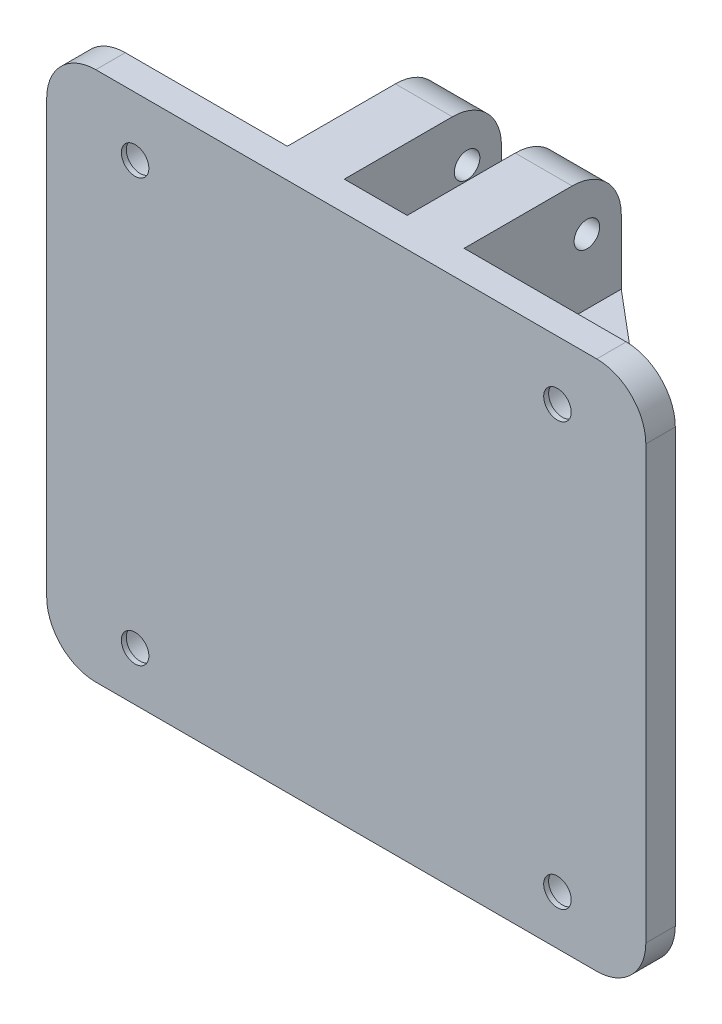
SolidWorks part; units mm, degrees
ref_plane "前视基准面" through (0, 0, 0) normal (0, 0, 1) x (1, 0, 0)
ref_plane "上视基准面" through (0, 0, 0) normal (0, 1, 0) x (1, 0, 0)
ref_plane "右视基准面" through (0, 0, 0) normal (1, 0, 0) x (0, 0, -1)
other "Configuration Table"
sketch "61 x 61 radar platform profile" plane through (0, 0, 0) normal (0, 0, 1) x (1, 0, 0)
  line L0 (31.5, 47.5) -> (82.5, 47.5)
  line L1 (87.5, 52.5) -> (87.5, 103.5)
  line L2 (82.5, 108.5) -> (31.5, 108.5)
  line L3 (26.5, 103.5) -> (26.5, 52.5)
  arc A0 (82.5, 47.5) -> (87.5, 52.5) centre (82.5, 52.5) ccw
  arc A1 (87.5, 103.5) -> (82.5, 108.5) centre (82.5, 103.5) ccw
  arc A2 (31.5, 108.5) -> (26.5, 103.5) centre (31.5, 103.5) ccw
  arc A3 (26.5, 52.5) -> (31.5, 47.5) centre (31.5, 52.5) ccw
extrude "61 x 61 radar platform" add sketch "61 x 61 radar platform profile" along normal blind 3 from offset 18
sketch "C1 four clearances 43 x 43 mm profile" plane through (0, 0, 0) normal (0, 0, 1) x (1, 0, 0)
  circle A0 centre (35.5, 59.5) radius 1.4
  circle A1 centre (35.5, 102.5) radius 1.4
  circle A2 centre (78.5, 59.5) radius 1.4
  circle A3 centre (78.5, 102.5) radius 1.4
  point P8 (26.5, 47.5)
  dimension "D3" = 2.8
  dimension "D6" = 2.8
  dimension "D9" = 2.8
  dimension "D12" = 2.8
  dimension "D1" = 9
  dimension "D2" = 12
  dimension "D4" = 9
  dimension "D5" = 55
  dimension "D7" = 52
  dimension "D8" = 12
  dimension "D10" = 52
  dimension "D11" = 55
extrude "C1 four clearances 43 x 43 mm" cut sketch "C1 four clearances 43 x 43 mm profile" along normal blind 5.2 from offset 17.9
sketch "C1 screw head pockets profile" plane through (0, 0, 0) normal (0, 0, 1) x (1, 0, 0)
  circle A0 centre (35.5, 59.5) radius 2.55
  circle A1 centre (35.5, 102.5) radius 2.55
  circle A2 centre (78.5, 59.5) radius 2.55
  circle A3 centre (78.5, 102.5) radius 2.55
  point P8 (26.5, 47.5)
  dimension "D3" = 5.1
  dimension "D6" = 5.1
  dimension "D9" = 5.1
  dimension "D12" = 5.1
  dimension "D1" = 9
  dimension "D2" = 12
  dimension "D4" = 9
  dimension "D5" = 55
  dimension "D7" = 52
  dimension "D8" = 12
  dimension "D10" = 52
  dimension "D11" = 55
extrude "C1 screw head pockets" cut sketch "C1 screw head pockets profile" along normal blind 2.6 from offset 17.9
sketch "草图3" plane through (0, 0, 18) normal (0, 0, -1) x (-1, 0, 0)
  line L0 (-82.5, 108.5) -> (-31.5, 108.5) construction
  line L1 (-66, 108.5) -> (-60.2, 108.5)
  line L2 (-66, 108.5) -> (-66, 47.5)
  line L3 (-66, 47.5) -> (-60.2, 47.5)
  line L4 (-60.2, 108.5) -> (-60.2, 47.5)
  line L5 (-31.5, 47.5) -> (-82.5, 47.5) construction
  line L6 (-87.5, 52.5) -> (-87.5, 103.5) construction
  line L7 (-53.8, 108.5) -> (-48, 108.5)
  line L8 (-53.8, 108.5) -> (-53.8, 47.5)
  line L9 (-53.8, 47.5) -> (-48, 47.5)
  line L10 (-48, 108.5) -> (-48, 47.5)
  line L11 (-26.5, 103.5) -> (-26.5, 52.5) construction
  dimension "D1" = 21.5
  dimension "D2" = 5.8
  dimension "D3" = 5.8
  dimension "D4" = 21.5
extrude "凸台-拉伸2" add sketch "草图3" along normal blind 16
sketch "草图4" plane through (66, 0, 0) normal (1, 0, 0) x (0, 0, -1)
  line L0 (-18, 108.5) -> (-18, 47.5) construction
  line L1 (-2, 108.5) -> (-18, 108.5) construction
  circle A0 centre (-15.5, 103.5) radius 1.3
  circle A1 centre (-15.5, 74.5) radius 1.3
  circle A2 centre (-5.5, 103.5) radius 1.3
  circle A3 centre (-5.5, 74.5) radius 1.3
  dimension "D1" = 2.5
  dimension "D2" = 5
  dimension "D3" = 2
  dimension "D4" = 2
extrude "切除-拉伸4" cut sketch "草图4" against normal blind 25
sketch "草图5" plane through (66, 0, 0) normal (1, 0, 0) x (0, 0, -1)
  line L0 (-18, 108.5) -> (-18, 47.5) construction
  line L1 (-18, 96.9) -> (-2, 96.9)
  line L2 (-18, 96.9) -> (-18, 79.1)
  line L3 (-18, 79.1) -> (-2, 79.1)
  line L4 (-2, 96.9) -> (-2, 79.1)
  line L5 (-2, 108.5) -> (-2, 47.5) construction
  circle A0 centre (-15.5, 103.5) radius 1.3 construction
  circle A1 centre (-5.5, 74.5) radius 1.3 construction
  dimension "D1" = 6.6
  dimension "D2" = 4.6
extrude "凸台-拉伸3" add sketch "草图5" along normal blind 19
sketch "草图6" plane through (0, 0, 18) normal (0, 0, -1) x (-1, 0, 0)
  line L0 (-48, 47.5) -> (-48, 108.5) construction
  line L1 (-48, 96.9) -> (-29, 96.9)
  line L2 (-48, 96.9) -> (-48, 79.1)
  line L3 (-48, 79.1) -> (-29, 79.1)
  line L4 (-29, 96.9) -> (-29, 79.1)
  line L9 (-85, 96.9) -> (-66, 96.9) construction
  dimension "D1" = 19
  dimension "D2" = 17.8
extrude "凸台-拉伸4" add sketch "草图6" along normal blind 16
sketch "草图7" plane through (0, 96.9, 0) normal (0, 1, 0) x (1, 0, 0)
  line L0 (66, -2) -> (85, -2)
  line L1 (85, -2) -> (85, -18)
  line L2 (85, -18) -> (66, -2)
  line L8 (48, -2) -> (29, -2)
  line L9 (48, -2) -> (48, -18) construction
  line L10 (48, -2) -> (48, -18) construction
  line L11 (29, -2) -> (29, -18)
  line L12 (29, -18) -> (48, -2)
extrude "切除-拉伸5" cut sketch "草图7" against normal blind 25.9
fillet "圆角4" radius 7 2 edges at (29, 88, 18) (85, 88, 18)
sketch "草图8" plane through (0, 0, 21) normal (0, 0, 1) x (1, 0, 0)
  line L0 (26.5, 103.5) -> (26.5, 52.5) construction
  line L1 (26.5, 54.5) -> (87.5608, 54.5)
  line L2 (26.5, 54.5) -> (26.5, 47.4392)
  line L3 (26.5, 47.4392) -> (87.5608, 47.4392)
  line L4 (87.5608, 54.5) -> (87.5608, 47.4392)
  circle A0 centre (35.5, 59.5) radius 1.4 construction
  dimension "D1" = 5
extrude "切除-拉伸6" cut sketch "草图8" against normal blind 25.9
fillet "圆角5" radius 5 6 edges at (26.5, 54.5, 19.5) (87.5, 54.5, 19.5) (63.1, 108.5, 2) (50.9, 108.5, 2) (50.9, 54.5, 2) (63.1, 54.5, 2)
